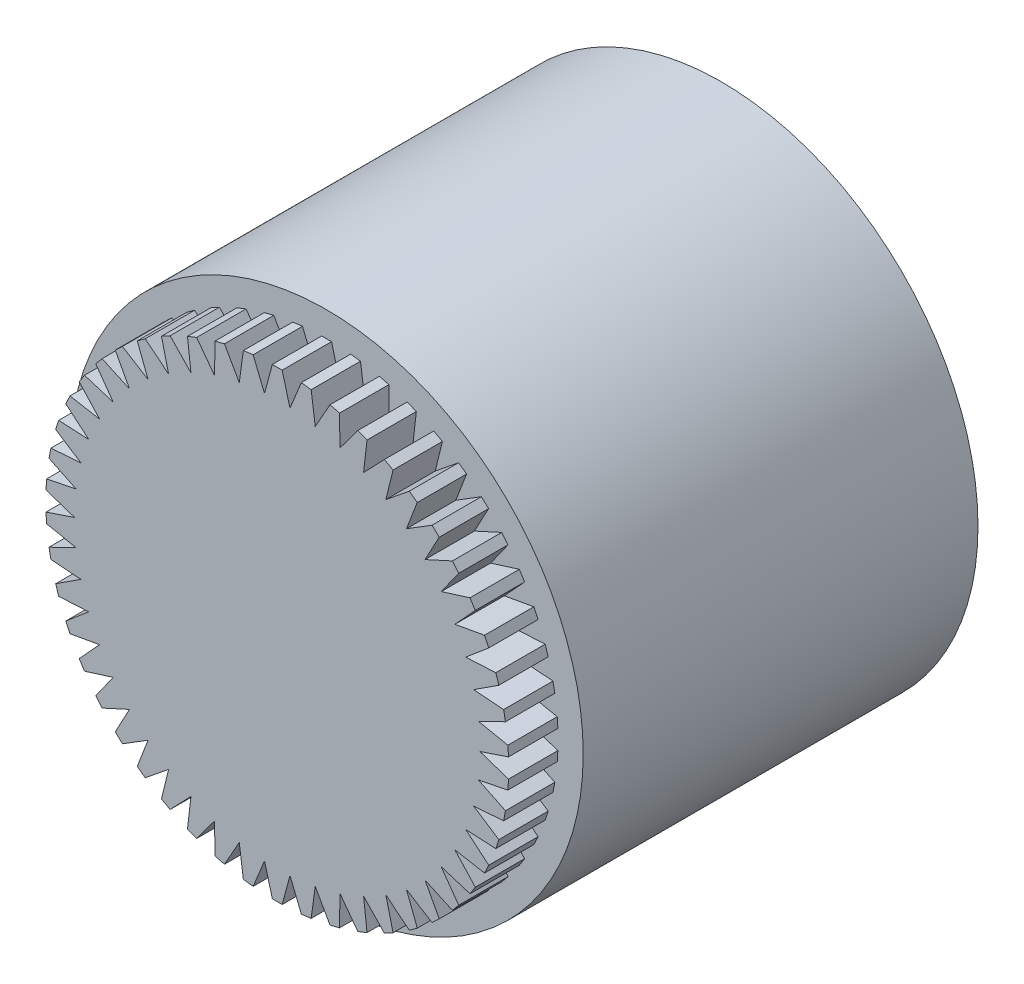
SolidWorks part; units mm, degrees
ref_plane "Front Plane" through (0, 0, 0) normal (0, 0, 1) x (1, 0, 0)
ref_plane "Top Plane" through (0, 0, 0) normal (0, 1, 0) x (1, 0, 0)
ref_plane "Right Plane" through (0, 0, 0) normal (1, 0, 0) x (0, 0, -1)
sketch "Sketch1" plane through (0, 0, 0) normal (0, 0, 1) x (1, 0, 0)
  circle A0 centre (0, 0) radius 26
  dimension "D1" = 52
extrude "Boss-Extrude1" add sketch "Sketch1" along normal blind 40
sketch "Sketch2" plane through (0, 0, 40) normal (0, 0, 1) x (1, 0, 0)
  circle A0 centre (0, 0) radius 20
  dimension "D1" = 40
extrude "Boss-Extrude2" add sketch "Sketch2" along normal blind 5
sketch "Sketch3" plane through (0, 0, 45) normal (0, 0, 1) x (1, 0, 0)
  line L0 (0, 0) -> (0, 23.4454) construction
  line L1 (0, 23.4454) -> (-0.5, 23.4454)
  line L2 (-0.5, 23.4454) -> (-1.7978, 18.6021)
  line L3 (0, 23.4454) -> (0.5, 23.4454)
  line L4 (0.5, 23.4454) -> (1.7978, 18.6021)
  line L5 (1.7978, 18.6021) -> (-1.7978, 18.6021)
  dimension "D1" = 0.5
  dimension "D2" = 0.5
  dimension "D3" = 75
  dimension "D4" = 75
  dimension "D5" = 23.4454
  dimension "D6" = 18.6021
extrude "Boss-Extrude3" add sketch "Sketch3" against normal blind 5
pattern_circular "CirPattern1" count 50 over 360 about axis through (0, 0, 45) along (0, 0, -1) of "Boss-Extrude3" reverse direction yes
sketch "Sketch4" plane through (0, 0, 0) normal (0, 0, -1) x (-1, 0, 0)
  circle A0 centre (0, 0) radius 6.75
  dimension "D1" = 13.5
